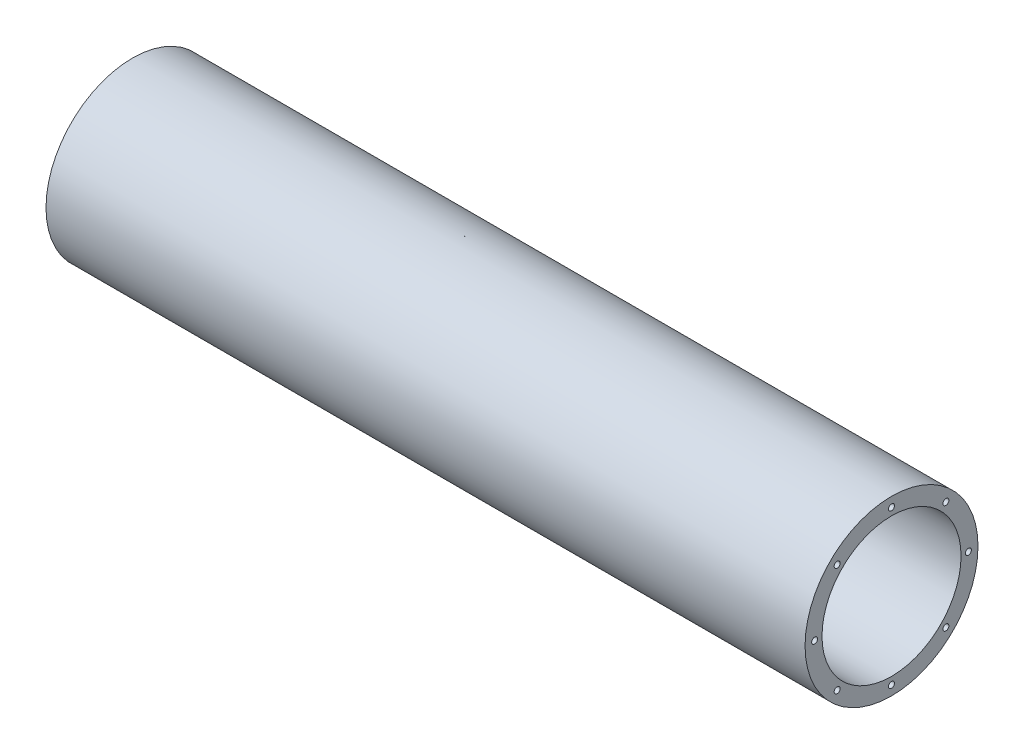
SolidWorks part; units mm, degrees
material "7075-T6 (SN)"
ref_plane "Front Plane" through (0, 0, 0) normal (0, 0, 1) x (1, 0, 0)
ref_plane "Top Plane" through (0, 0, 0) normal (0, 1, 0) x (1, 0, 0)
ref_plane "Right Plane" through (0, 0, 0) normal (1, 0, 0) x (0, 0, -1)
sketch "Sketch1" plane through (0, 0, 0) normal (1, 0, 0) x (0, 0, -1)
  circle A0 centre (0, 0) radius 45.9486
  circle A1 centre (0, 0) radius 57.15
  dimension "D1" = 91.8972
  dimension "D2" = 114.3
extrude "Boss-Extrude1" add sketch "Sketch1" along normal blind 501.65
sketch "Sketch2" plane through (0, 0, 0) normal (-1, 0, 0) x (0, 0, 1)
  circle A0 centre (0, 0) radius 44.5262
  circle A1 centre (0, 0) radius 45.9486
  dimension "D1" = 89.0524
extrude "Boss-Extrude2" add sketch "Sketch2" against normal blind 76.2
sketch "Sketch3" plane through (0, 0, 0) normal (-1, 0, 0) x (0, 0, 1)
  circle A0 centre (0, 0) radius 50.8 construction
  circle A1 centre (0, 50.8) radius 1.9844
  circle A2 centre (35.921, 35.921) radius 1.9844
  circle A3 centre (50.8, 0) radius 1.9844
  circle A4 centre (35.921, -35.921) radius 1.9844
  circle A5 centre (0, -50.8) radius 1.9844
  circle A6 centre (-35.921, -35.921) radius 1.9844
  circle A7 centre (-50.8, 0) radius 1.9844
  circle A8 centre (-35.921, 35.921) radius 1.9844
  point P22 (0, 0)
  dimension "D1" = 101.6
  dimension "D2" = 3.9688
  dimension "D3" = 8
extrude "Cut-Extrude1" cut sketch "Sketch3" against normal blind 13.97
sketch "Sketch4" plane through (501.65, 0, 0) normal (1, 0, 0) x (0, 0, -1)
  circle A0 centre (0, 0) radius 50.8 construction
  circle A1 centre (0, 50.8) radius 1.9844
  circle A2 centre (35.921, 35.921) radius 1.9844
  circle A3 centre (50.8, 0) radius 1.9844
  circle A4 centre (35.921, -35.921) radius 1.9844
  circle A5 centre (0, -50.8) radius 1.9844
  circle A6 centre (-35.921, -35.921) radius 1.9844
  circle A7 centre (-50.8, 0) radius 1.9844
  circle A8 centre (-35.921, 35.921) radius 1.9844
  point P21 (0, 0)
  dimension "D1" = 101.6
  dimension "D2" = 3.9688
  dimension "D3" = 8
extrude "Cut-Extrude2" cut sketch "Sketch4" against normal blind 13.97
